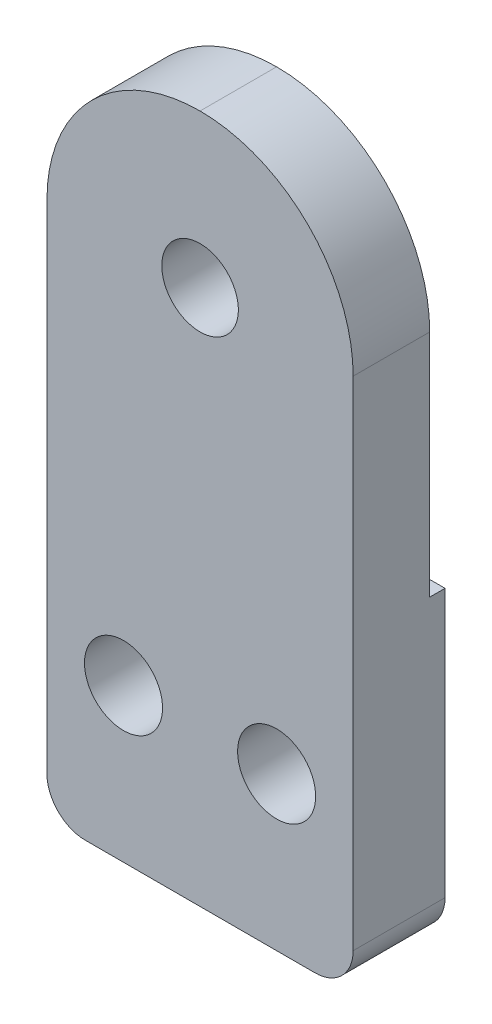
SolidWorks part; units mm, degrees
ref_plane "Front Plane" through (0, 0, 0) normal (0, 0, 1) x (1, 0, 0)
ref_plane "Top Plane" through (0, 0, 0) normal (0, 1, 0) x (1, 0, 0)
ref_plane "Right Plane" through (0, 0, 0) normal (1, 0, 0) x (0, 0, -1)
sketch "Sketch1" plane through (0, 0, 0) normal (0, 0, 1) x (1, 0, 0)
  line L1 (10, -22.5) -> (-10, -22.5)
  line L2 (10, -22.5) -> (10, 22.5)
  line L3 (10, 22.5) -> (-10, 22.5)
  line L4 (-10, -22.5) -> (-10, 22.5)
  line L5 (10, -22.5) -> (-10, 22.5) construction
  line L6 (10, 22.5) -> (-10, -22.5) construction
  point P0 (0, 0)
  dimension "D1" = 20
  dimension "D2" = 45
extrude "Boss-Extrude1" add sketch "Sketch1" along normal blind 6
fillet "Fillet2" radius 10 2 edges at (-10, 22.5, 3) (10, 22.5, 3)
sketch "Sketch2" plane through (0, 0, 0) normal (0, 0, -1) x (-1, 0, 0)
  circle A0 centre (0, 12.5) radius 2.5
  dimension "D1" = 5
extrude "Cut-Extrude1" cut sketch "Sketch2" against normal through all
sketch "Sketch3" plane through (0, 0, 0) normal (0, 0, -1) x (-1, 0, 0)
  line L0 (10, -22.5) -> (-10, -22.5) construction
  line L1 (10, 12.5) -> (10, -22.5) construction
  circle A0 centre (-5, -12.5) radius 2.55
  circle A1 centre (5, -12.5) radius 2.55
  dimension "D1" = 5.1
  dimension "D2" = 10
  dimension "D4" = 5.1
  dimension "D6" = 10
  dimension "D3" = 15
  dimension "D5" = 10
extrude "Cut-Extrude2" cut sketch "Sketch3" against normal through all
fillet "Fillet3" radius 2.5 2 edges at (-10, -22.5, 3) (10, -22.5, 3)
sketch "Sketch4" plane through (0, 0, 0) normal (0, 0, -1) x (-1, 0, 0)
  line L0 (7.5, -22.5) -> (-7.5, -22.5) construction
  line L1 (-20, 27.5) -> (20, 27.5)
  line L2 (-20, 27.5) -> (-20, -2.5)
  line L3 (-20, -2.5) -> (20, -2.5)
  line L4 (20, 27.5) -> (20, -2.5)
  line L5 (-20, 27.5) -> (20, -2.5) construction
  line L6 (-20, -2.5) -> (20, 27.5) construction
  point P0 (0, 12.5)
  dimension "D1" = 20
  dimension "D2" = 40
extrude "Cut-Extrude3" cut sketch "Sketch4" against normal blind 1
